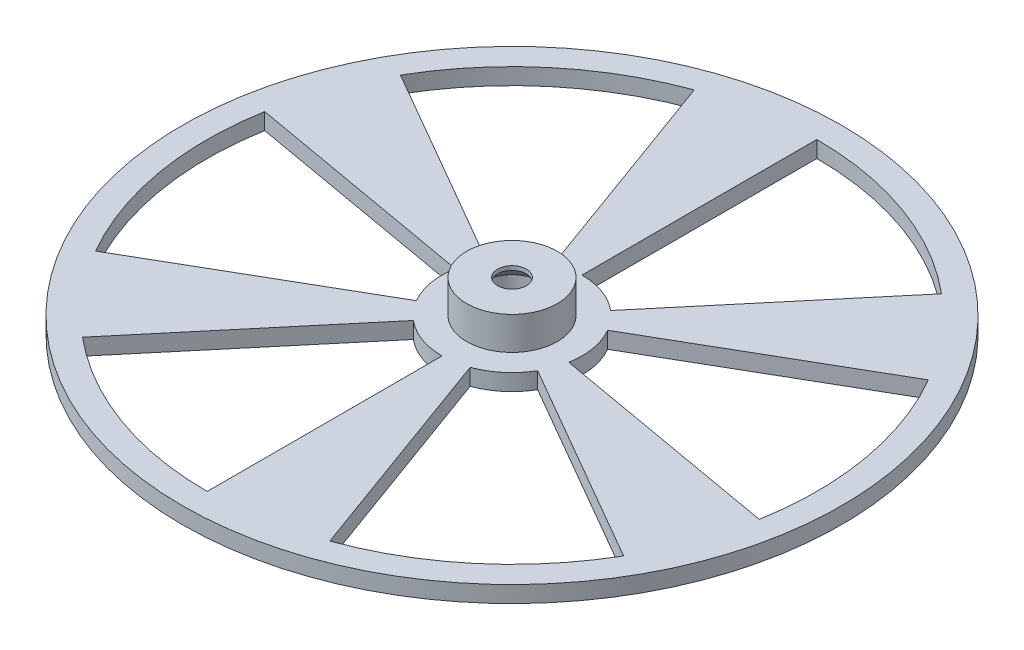
SolidWorks part; units mm, degrees
ref_plane "Alzado" through (0, 0, 0) normal (0, 0, 1) x (1, 0, 0)
ref_plane "Planta" through (0, 0, 0) normal (0, 1, 0) x (1, 0, 0)
ref_plane "Vista lateral" through (0, 0, 0) normal (1, 0, 0) x (0, 0, -1)
sketch "Croquis1" plane through (0, 0, 0) normal (0, 1, 0) x (1, 0, 0)
  circle A0 centre (0, 0) radius 40
  dimension "D1" = 80
extrude "Saliente-Extruir1" add sketch "Croquis1" along normal blind 2
sketch "Croquis2" plane through (0, 2, 0) normal (0, 1, 0) x (1, 0, 0)
  circle A0 centre (0, 0) radius 5.5
  dimension "D1" = 11
extrude "Saliente-Extruir2" add sketch "Croquis2" along normal blind 4
sketch "Croquis3" plane through (0, 6, 0) normal (0, 1, 0) x (1, 0, 0)
  circle A0 centre (0, 0) radius 1.75
  dimension "D1" = 3.5
extrude "Cortar-Extruir1" cut sketch "Croquis3" against normal through all
sketch "Croquis4" plane through (0, 0, 0) normal (0, -1, 0) x (-1, 0, 0)
  circle A0 centre (0, 0) radius 3.25
  dimension "D1" = 6.5
extrude "Cortar-Extruir2" cut sketch "Croquis4" against normal blind 3.5
chamfer "Chaflán1" distance 2 angle 45 1 edges at (0, 3.5, -1.75)
sketch "Croquis5" plane through (0, 2, 0) normal (0, 1, 0) x (1, 0, 0)
  line L0 (0, 8.5) -> (0, 37)
  line L1 (23.7831, 28.3436) -> (5.4637, 6.5114)
  line L2 (5.4637, 6.5114) -> (0, 0) construction
  line L3 (7.3612, 4.25) -> (32.0429, 18.5)
  line L4 (36.4379, -6.425) -> (8.3709, -1.476)
  line L5 (7.3612, -4.25) -> (32.0429, -18.5)
  line L6 (12.6547, -34.7686) -> (2.9072, -7.9874)
  line L7 (0, -8.5) -> (0, -37)
  line L8 (-23.7831, -28.3436) -> (-5.4637, -6.5114)
  line L9 (-7.3612, -4.25) -> (-32.0429, -18.5)
  line L10 (-36.4379, 6.425) -> (-8.3709, 1.476)
  line L11 (-7.3612, 4.25) -> (-32.0429, 18.5)
  line L12 (-12.6547, 34.7686) -> (-2.9072, 7.9874)
  arc A0 (23.7831, 28.3436) -> (0, 37) centre (0, 0) ccw
  arc A1 (5.4637, 6.5114) -> (0, 8.5) centre (0, 0) ccw
  circle A2 centre (0, 0) radius 40 construction
  circle A3 centre (0, 0) radius 5.5 construction
  arc A4 (36.4379, -6.425) -> (32.0429, 18.5) centre (0, 0) ccw
  arc A5 (8.3709, -1.476) -> (7.3612, 4.25) centre (0, 0) ccw
  arc A6 (12.6547, -34.7686) -> (32.0429, -18.5) centre (0, 0) ccw
  arc A7 (2.9072, -7.9874) -> (7.3612, -4.25) centre (0, 0) ccw
  arc A8 (-23.7831, -28.3436) -> (0, -37) centre (0, 0) ccw
  arc A9 (-5.4637, -6.5114) -> (0, -8.5) centre (0, 0) ccw
  arc A10 (-36.4379, 6.425) -> (-32.0429, -18.5) centre (0, 0) ccw
  arc A11 (-8.3709, 1.476) -> (-7.3612, -4.25) centre (0, 0) ccw
  arc A12 (-12.6547, 34.7686) -> (-32.0429, 18.5) centre (0, 0) ccw
  arc A13 (-2.9072, 7.9874) -> (-7.3612, 4.25) centre (0, 0) ccw
  dimension "D2" = 3
  dimension "D3" = 6
  dimension "D1" = 40
  dimension "3" = 3
extrude "Cortar-Extruir3" cut sketch "Croquis5" against normal through all
